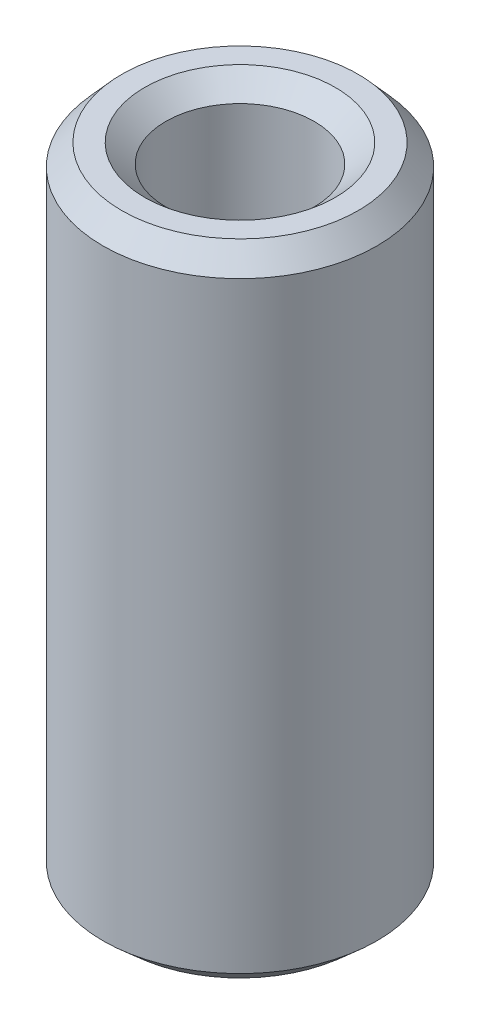
SolidWorks part; units mm, degrees
ref_plane "Front Plane" through (0, 0, 0) normal (0, 0, 1) x (1, 0, 0)
ref_plane "Top Plane" through (0, 0, 0) normal (0, 1, 0) x (1, 0, 0)
ref_plane "Right Plane" through (0, 0, 0) normal (1, 0, 0) x (0, 0, -1)
sketch "Sketch1" plane through (0, 0, 0) normal (0, 1, 0) x (1, 0, 0)
  circle A0 centre (0, 0) radius 20
  dimension "SLEEVE_OD" = 40
extrude "Boss-Extrude1" add sketch "Sketch1" along normal blind 93.7117
sketch "Sketch2" plane through (0, 0, 0) normal (0, 1, 0) x (1, 0, 0)
  circle A0 centre (0, 0) radius 10.8298
  dimension "BORE_D" = 21.6595
extrude "Cut-Extrude1" cut sketch "Sketch2" along normal through all
chamfer "Chamfer1" distance 3.0922 angle 41.591 4 edges at (0, 93.7117, 10.8298) (0, 0, 10.8298) (0, 0, 20) (0, 93.7117, 20) first distance on face at (0, 93.7117, 10.8298) first distance on face at (0, 0, 10.8298) first distance on face at (0, 93.7117, 20)
